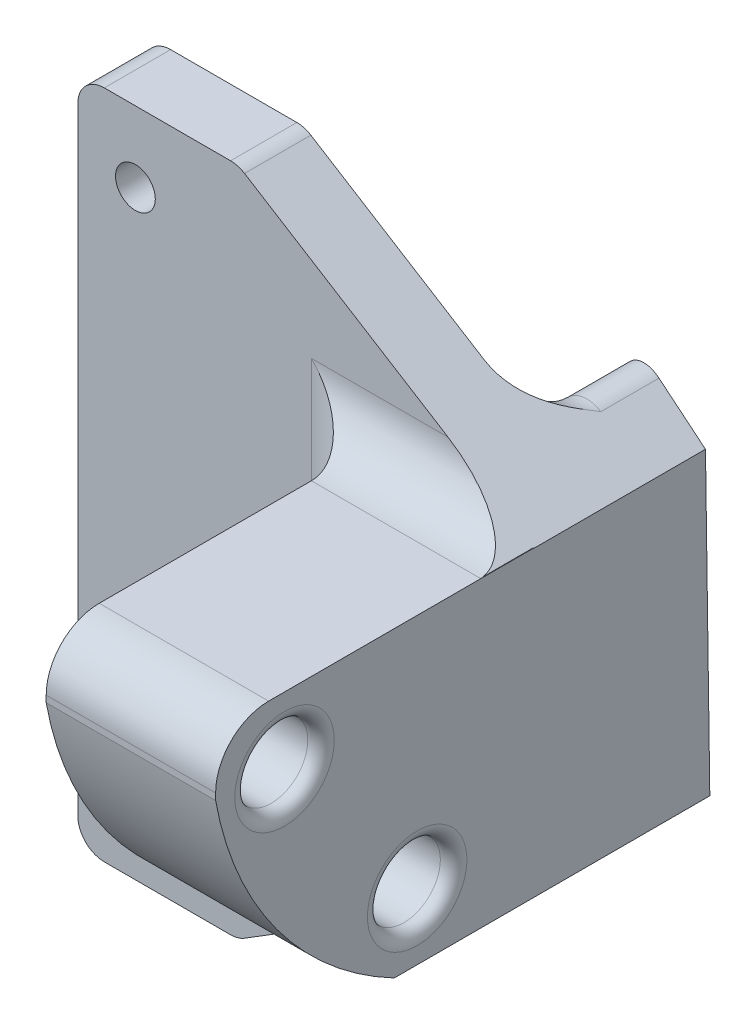
SolidWorks part; units mm, degrees
ref_plane "Front" through (0, 0, 0) normal (0, 0, 1) x (1, 0, 0)
ref_plane "Top" through (0, 0, 0) normal (0, 1, 0) x (1, 0, 0)
ref_plane "Right" through (0, 0, 0) normal (1, 0, 0) x (0, 0, -1)
sketch "Sketch1" plane through (0, 0, 0) normal (0, 0, 1) x (1, 0, 0)
  line L0 (-2.1711, 12.6384) -> (-2.1711, -12.6384)
  line L1 (-2.1711, 12.6384) -> (3.8736, 12.6384)
  line L2 (3.8736, 12.6384) -> (13.1359, 5.7111)
  line L3 (-2.1711, -12.6384) -> (3.8736, -12.6384)
  line L4 (0, 9.9704) -> (0, -9.9704) construction
  line L5 (8.6359, 5.7111) -> (13.1359, 5.7111)
  line L6 (8.6359, 5.7111) -> (8.6359, -5.7111)
  line L7 (8.6359, -5.7111) -> (13.1359, -5.7111)
  line L8 (13.1359, 5.7111) -> (13.1359, -5.7111)
  line L9 (0, 0) -> (8.6359, 0)
  line L10 (3.8736, -12.6384) -> (13.1359, -5.7111)
  line L11 (-7.975, 3.0296) -> (17.9467, 3.0296)
  line L12 (-7.975, -3.0296) -> (17.5996, -3.0296)
  line L13 (11.7914, -1.6546) -> (13.1359, -1.6546)
  line L14 (11.7914, -1.6546) -> (11.7914, -4.4046)
  line L15 (11.7914, -4.4046) -> (13.1359, -4.4046)
  line L16 (13.1359, -1.6546) -> (13.1359, -4.4046)
  line L17 (13.1359, 1.7482) -> (11.7914, 1.7482)
  line L18 (13.1359, 1.7482) -> (13.1359, 4.3111)
  line L19 (13.1359, 4.3111) -> (11.7914, 4.3111)
  line L20 (11.7914, 1.7482) -> (11.7914, 4.3111)
  circle A0 centre (0, 9.9704) radius 0.75
  circle A1 centre (0, -9.9704) radius 0.75
  point P8 (-2.1711, 0)
  point P17 (8.6359, 0)
  point P28 (11.7914, 3.0296)
  point P29 (11.7914, -3.0296)
  dimension "D5" = 1.5
  dimension "D1" = 4.5
  dimension "D2" = 2.75
  dimension "D3" = 1.4
  dimension "D4" = 19.9407
sketch "Sketch2" plane through (0, 0, 0) normal (0, 0, 1) x (1, 0, 0)
  line L1 (-2.1711, -12.6384) -> (3.8736, -12.6384) construction
  line L2 (-2.1711, 12.6384) -> (-2.1711, -12.6384) construction
  line L3 (-2.1711, 12.6384) -> (3.8736, 12.6384) construction
  line L5 (4.1162, -12.4875) -> (15.0245, -5.7)
  line L6 (-1.1711, -12.6384) -> (3.5879, -12.6384)
  line L7 (-2.1711, 11.6384) -> (-2.1711, -11.6384)
  line L8 (-1.1711, 12.6384) -> (3.5879, 12.6384)
  line L9 (4.1162, 12.4875) -> (15.0245, 5.7)
  line L10 (15.0245, 5.7) -> (15.0245, -5.7)
  circle A0 centre (0, -9.9704) radius 0.75 construction
  circle A1 centre (0, 9.9704) radius 0.75 construction
  circle A2 centre (0, -9.9704) radius 0.75
  circle A3 centre (0, 9.9704) radius 0.75
  arc A4 (4.1162, -12.4875) -> (3.5879, -12.6384) centre (3.5879, -11.6384) cw
  arc A5 (-1.1711, -12.6384) -> (-2.1711, -11.6384) centre (-1.1711, -11.6384) cw
  arc A6 (3.5879, 12.6384) -> (4.1162, 12.4875) centre (3.5879, 11.6384) cw
  arc A7 (-2.1711, 11.6384) -> (-1.1711, 12.6384) centre (-1.1711, 11.6384) cw
  point P25 (15.0245, 0)
  dimension "D1" = 1
  dimension "D2" = 11.4
extrude "Boss-Extrude1" add sketch "Sketch2" along normal blind 2.5
sketch "Sketch4" plane through (15.0245, 0, 0) normal (1, 0, 0) x (0, 0, -1)
  line L0 (50, 0) -> (-50, 0) construction
  circle A0 centre (-11.9, 3.2) radius 1.375
  circle A1 centre (-6.9, -3.2) radius 1.375
  dimension "D3" = 2.75
  dimension "D4" = 2.75
  dimension "D1" = 3.2
  dimension "D2" = 3.2
sketch "Sketch3" plane through (0, 0, 2.5) normal (0, 0, 1) x (1, 0, 0)
  line L4 (8.6359, 5.7111) -> (15.0245, 5.7111)
  line L5 (8.6359, 5.7111) -> (8.6359, -5.7)
  line L6 (8.6359, -5.7) -> (15.0245, -5.7)
  line L7 (15.0245, 5.7111) -> (15.0245, -5.7)
extrude "Boss-Extrude2" add sketch "Sketch3" along normal blind 12
sketch "Sketch5" plane through (15.0245, 0, 0) normal (1, 0, 0) x (0, 0, -1)
  line L0 (-14.5, -5.7) -> (-2.5, -5.7) construction
  line L1 (-14.5, -5.7) -> (-14.5, 5.7111) construction
  line L2 (-7.7623, -5.7) -> (-14.5, -5.7)
  line L3 (-14.5, -5.7) -> (-14.5, 3.4649)
  arc A0 (-7.7623, -5.7) -> (-14.5, 3.4649) centre (-1.774, 5.7615) cw
extrude "Cut-Extrude1" cut sketch "Sketch5" against normal through all
sketch "Sketch6" plane through (15.0245, 0, 0) normal (1, 0, 0) x (0, 0, -1)
  circle A0 centre (-6.9, -3.2) radius 1.375 construction
  circle A1 centre (-11.9, 3.2) radius 1.375 construction
  circle A2 centre (-6.9, -3.2) radius 1.375
  circle A3 centre (-11.9, 3.2) radius 1.375
extrude "Cut-Extrude2" cut sketch "Sketch6" against normal blind 4
sketch "Sketch7" plane through (11.0245, 0, 0) normal (1, 0, 0) x (0, 0, -1)
  circle A0 centre (-11.9, 3.2) radius 0.75
  circle A1 centre (-6.9, -3.2) radius 0.75
  dimension "D1" = 1.5
extrude "Cut-Extrude3" cut sketch "Sketch7" against normal blind 3
fillet "Fillet1" radius 2 3 edges at (11.8213, 5.7111, 2.5) (8.6359, 0.0055, 2.5) (11.8302, -5.7, 2.5)
sketch3d "3DSketch1"
  line L27 (0.4693, -5.2406, -5.9744) -> (22.81, -10.7228, -3.3746)
  line L33 (29.1147, 15.5064, -2.2423) -> (9.1866, 20.3966, -4.5614)
ref_plane "Plane1" through (0.7038, 0.0842, -5.8699) normal (-0.119, -0.0142, 0.9928) x (0.9929, -0.0017, 0.119)
sketch "Sketch8" plane through (0, 0, 0) normal (0, 0, -1) x (-1, 0, 0)
  line L0 (-11.5245, 7.8778) -> (-11.5245, -7.8778)
  line L6 (-15.0245, 5.7) -> (-15.0245, -5.7)
  line L7 (-15.0245, -5.7) -> (-4.1162, -12.4875)
  line L8 (-3.5879, -12.6384) -> (1.1711, -12.6384)
  line L9 (2.1711, -11.6384) -> (2.1711, 11.6384)
  line L10 (1.1711, 12.6384) -> (-3.5879, 12.6384)
  line L11 (-4.1162, 12.4875) -> (-15.0245, 5.7)
  line L12 (-15.0245, 5.7) -> (-15.0245, -5.7)
  line L13 (-15.0245, -5.7) -> (-11.5245, -7.8778)
  line L17 (-11.5245, 7.8778) -> (-15.0245, 5.7)
  arc A4 (-4.1162, -12.4875) -> (-3.5879, -12.6384) centre (-3.5879, -11.6384) ccw
  arc A5 (1.1711, -12.6384) -> (2.1711, -11.6384) centre (1.1711, -11.6384) ccw
  arc A6 (2.1711, 11.6384) -> (1.1711, 12.6384) centre (1.1711, 11.6384) ccw
  arc A7 (-3.5879, 12.6384) -> (-4.1162, 12.4875) centre (-3.5879, 11.6384) ccw
  dimension "D2" = 3.5
  dimension "D1" = 0
extrude "Boss-Extrude3" add sketch "Sketch8" along normal offset from surface (4.5861 mm away) 0.1 up to plane "Plane1"
fillet "Fillet2" radius 1 2 edges at (11.5245, 7.8778, -2.18) (11.5245, -7.8778, -2.2931)
fillet "Fillet3" radius 2 3 edges at (12.0389, -6.952, 0) (12.0389, 6.952, 0) (11.5245, 0, 0)
fillet "Fillet4" radius 0.5 4 edges at (8.6359, -2.45, 6.9) (8.6359, 3.95, 11.9) (15.0245, -3.2, 5.525) (15.0245, 3.2, 10.525)
fillet "Fillet5" radius 2 1 edges at (11.8302, 5.7111, 14.5)
sketch "Sketch9" plane through (0, 0, 0) normal (0, 1, 0) x (1, 0, 0)
  line L0 (13.6441, 3.2259) -> (11.6908, 3.2259)
  line L1 (11.6908, 3.2259) -> (5.0251, -0.4121)
  line L2 (5.0251, -0.4121) -> (13.1557, -0.4121)
  line L3 (13.1557, -0.4121) -> (13.6441, 3.2259)
extrude "Boss-Extrude4" add sketch "Sketch9" along normal mid plane 2
fillet "Fillet6" radius 1 6 edges at (11.5245, 1, -2.5676) (10.9388, 1, -0.5858) (11.5245, -1, -2.5676) (10.9388, -1, -0.5858) (7.6523, 1, 0) (7.6523, -1, 0)
